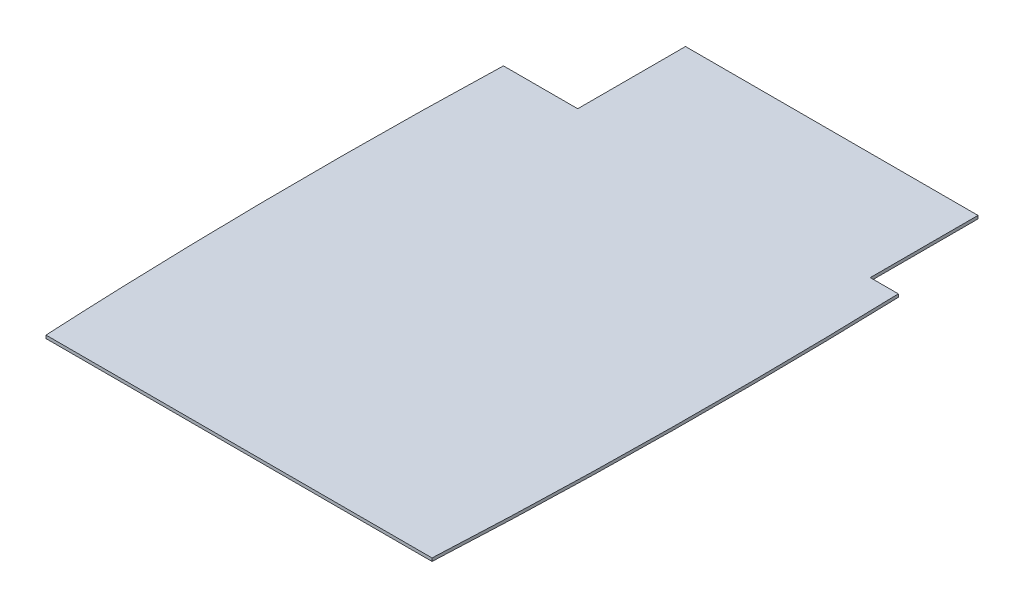
SolidWorks part; units mm, degrees
ref_plane "正面" through (0, 0, 0) normal (0, 0, 1) x (1, 0, 0)
ref_plane "平面" through (0, 0, 0) normal (0, 1, 0) x (1, 0, 0)
ref_plane "右側面" through (0, 0, 0) normal (1, 0, 0) x (0, 0, -1)
sketch "ｽｹｯﾁ1" plane through (0, 0, 0) normal (0, 1, 0) x (1, 0, 0)
  line L1 (-65, 92.5) -> (65, 92.5)
  line L2 (-65, 92.5) -> (-65, -92.5) construction
  line L3 (-65, -92.5) -> (65, -92.5)
  line L4 (65, 92.5) -> (65, -92.5) construction
  ellipse E0 centre (0, 0) end of major axis (0, -350) minor radius 65
  point P11 (-65, 0)
  dimension "D1" = 130
  dimension "D2" = 700
  dimension "D3" = 185
extrude "ﾎﾞｽ - 押し出し1" add sketch "ｽｹｯﾁ1" along normal mid plane 1 contours L3 E0 L1 region at (0, 0, 0)
sketch "ｽｹｯﾁ3" plane through (0, 0.5, 0) normal (0, 1, 0) x (1, 0, 0)
  line L0 (-62.6889, 92.5) -> (62.6889, 92.5) construction
  line L1 (-65, 92.5) -> (-40, 92.5)
  line L2 (-65, 92.5) -> (-65, 57.5)
  line L3 (-65, 57.5) -> (-40, 57.5)
  line L4 (-40, 92.5) -> (-40, 57.5)
  ellipse E0 centre (0, 0) end of major axis (0, -350) minor radius 65 (-62.6889, 92.5) -> (-62.6889, -92.5) ccw construction
  point P11 (0, 0)
  dimension "D1" = 35
  dimension "D2" = 25
extrude "ｶｯﾄ - 押し出し1" cut sketch "ｽｹｯﾁ3" against normal through all
sketch "ｽｹｯﾁ4" plane through (0, 0.5, 0) normal (0, 1, 0) x (1, 0, 0)
  line L0 (-40, 92.5) -> (62.6889, 92.5) construction
  line L1 (55, 92.5) -> (65, 92.5)
  line L2 (55, 92.5) -> (55, 57.5)
  line L3 (55, 57.5) -> (65, 57.5)
  line L4 (65, 92.5) -> (65, 57.5)
  line L5 (-64.1168, 57.5) -> (-40, 57.5) construction
  ellipse E0 centre (0, 0) end of major axis (0, -350) minor radius 65 (62.6889, -92.5) -> (62.6889, 92.5) ccw construction
  point P11 (0, 0)
  point P16 (0, 0)
  dimension "D1" = 10
extrude "ｶｯﾄ - 押し出し2" cut sketch "ｽｹｯﾁ4" against normal through all
